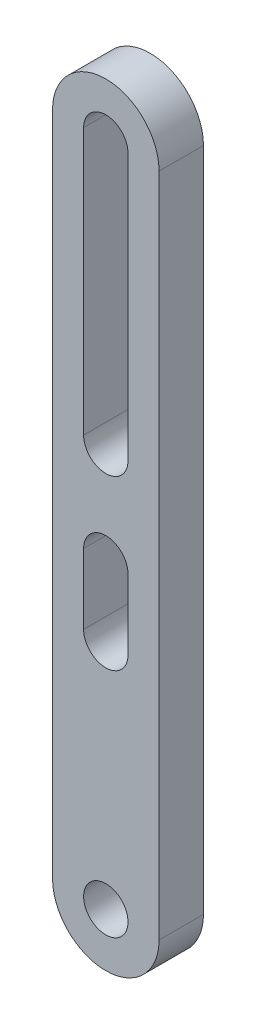
SolidWorks part; units mm, degrees
material "Plain Carbon Steel"
ref_plane "Front Plane" through (0, 0, 0) normal (0, 0, 1) x (1, 0, 0)
ref_plane "Top Plane" through (0, 0, 0) normal (0, 1, 0) x (1, 0, 0)
ref_plane "Right Plane" through (0, 0, 0) normal (1, 0, 0) x (0, 0, -1)
sketch "Sketch1" plane through (0, 0, 0) normal (0, 0, 1) x (1, 0, 0)
  line L0 (0, -2.75) -> (0, 2.75) construction
  line L1 (-6, 75) -> (-6, 0)
  line L2 (2.75, 0) -> (-2.75, 0) construction
  line L3 (6, 75) -> (6, 0)
  line L4 (-2.5, 75) -> (-2.5, 45)
  line L5 (2.5, 45) -> (2.5, 75)
  line L6 (2.5, 33.9486) -> (2.5, 26.0514)
  line L7 (-2.5, 33.9486) -> (-2.5, 26.0514)
  line L8 (-2.5, 30) -> (16.4415, 30) construction
  line L9 (-2.5, 45) -> (18.8328, 45) construction
  circle A0 centre (0, 0) radius 2.5
  arc A1 (2.5, 75) -> (-2.5, 75) centre (0, 75) ccw
  arc A2 (-6, 0) -> (6, 0) centre (0, 0) ccw
  arc A3 (6, 75) -> (-6, 75) centre (0, 75) ccw
  arc A4 (-2.5, 45) -> (2.5, 45) centre (0, 45) ccw
  arc A5 (2.5, 33.9486) -> (-2.5, 33.9486) centre (0, 33.9486) ccw
  arc A6 (-2.5, 26.0514) -> (2.5, 26.0514) centre (0, 26.0514) ccw
  dimension "D1" = 5
  dimension "D2" = 75
  dimension "D3" = 6
  dimension "D4" = 2.5
  dimension "D5" = 30
  dimension "D6" = 45
extrude "Boss-Extrude1" add sketch "Sketch1" along normal blind 5
